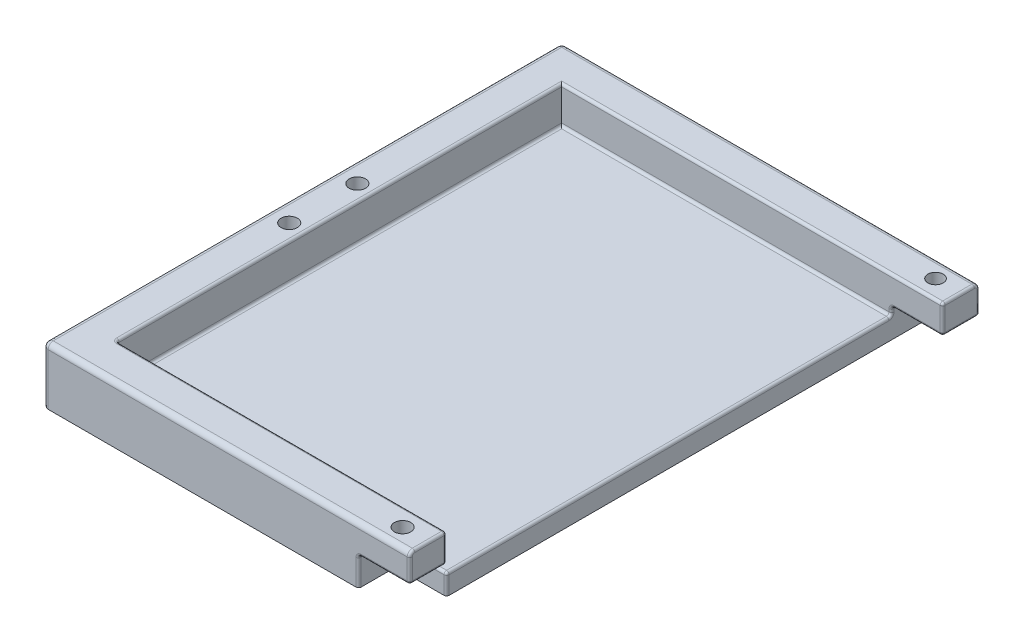
SolidWorks part; units mm, degrees
ref_plane "Front Plane" through (0, 0, 0) normal (0, 0, 1) x (1, 0, 0)
ref_plane "Top Plane" through (0, 0, 0) normal (0, 1, 0) x (1, 0, 0)
ref_plane "Right Plane" through (0, 0, 0) normal (1, 0, 0) x (0, 0, -1)
sketch "Sketch1" plane through (0, 0, 0) normal (0, 1, 0) x (1, 0, 0)
  line L1 (-35.85, 50.7) -> (35.85, 50.7)
  line L2 (-35.85, 50.7) -> (-35.85, -50.7)
  line L3 (-35.85, -50.7) -> (35.85, -50.7)
  line L4 (35.85, 50.7) -> (35.85, -50.7)
  line L5 (-35.85, 50.7) -> (35.85, -50.7) construction
  line L6 (-35.85, -50.7) -> (35.85, 50.7) construction
  point P0 (0, 0)
  dimension "D1" = 71.7
  dimension "D2" = 101.4
extrude "Boss-Extrude1" add sketch "Sketch1" along normal blind 11.1 contours L1 L4 L3 L2
sketch "Sketch5" plane through (35.85, 0, 0) normal (1, 0, 0) x (0, 0, -1)
  line L2 (-43.5, 18.4616) -> (-43.5, 4)
  line L3 (-43.5, 4) -> (43.5, 4)
  line L4 (0, 0) -> (0, 18.4616) construction
  line L5 (50.7, 0) -> (-50.7, 0) construction
  line L7 (-43.5, 18.4616) -> (43.5, 18.4616)
  line L8 (43.5, 18.4616) -> (43.5, 4)
  point P9 (0, 4)
  dimension "D1" = 87
  dimension "D3" = 4
extrude "Cut-Extrude1" cut sketch "Sketch5" against normal blind 64.5
fillet "Fillet2" radius 1 4 edges at (-35.85, 5.55, -50.7) (-35.85, 5.55, 50.7) (-35.85, 11.1, 0) (-35.85, 0, 0)
sketch "Sketch7" plane through (0, 11.1, 0) normal (0, 1, 0) x (1, 0, 0)
  line L0 (-35.85, 0) -> (0, 0) construction
  line L1 (-35.85, 50.7) -> (-35.85, -50.7) construction
  line L2 (-34.85, -6.6579) -> (-28.65, -6.6579) construction
  line L3 (-34.85, 50.7) -> (-34.85, -50.7) construction
  circle A0 centre (-31.75, -6.6579) radius 1.6
  circle A1 centre (-31.75, 6.6579) radius 1.6
  dimension "D1" = 3.2
  dimension "D2" = 6.6579
  dimension "D3" = 6.2
extrude "Cut-Extrude3" cut sketch "Sketch7" against normal blind 4
sketch "Sketch10" plane through (35.85, 0, 0) normal (1, 0, 0) x (0, 0, -1)
  line L0 (-43.5, 0) -> (-50.7, 0)
  line L1 (50.7, 0) -> (-50.7, 0) construction
  line L2 (-50.7, 11.1) -> (-50.7, 0) construction
  line L3 (-50.7, 5.55) -> (-50.7, 0)
  line L4 (-43.5, 5.55) -> (-43.5, 0)
  line L7 (-43.5, 11.1) -> (-43.5, 0) construction
  line L8 (-43.5, 11.1) -> (-43.5, 4) construction
  line L9 (-43.5, 5.55) -> (-43.5, 11.1)
  line L12 (-50.7, 5.55) -> (-43.5, 5.55)
  line M10 (-43.5, 4) -> (-43.5, 11.1)
  line M13 (-50.7, 11.1) -> (-50.7, 0)
  line M14 (-50.7, 0) -> (50.7, 0)
sketch "Sketch11" plane through (35.85, 0, 0) normal (1, 0, 0) x (0, 0, -1)
  line L0 (43.5, 11.1) -> (43.5, 0) construction
  line L1 (50.7, 0) -> (-50.7, 0) construction
  line L2 (50.7, 5.55) -> (50.7, 11.1)
  line L3 (50.7, 11.1) -> (43.5, 11.1) construction
  line L4 (43.5, 5.55) -> (50.7, 5.55)
  line L5 (50.7, 11.1) -> (50.7, 0) construction
  line L6 (50.7, 11.1) -> (43.5, 11.1)
  line L7 (43.5, 11.1) -> (50.7, 11.1)
  line L8 (43.5, 11.1) -> (43.5, 5.55)
  line M1 (50.7, 0) -> (50.7, 11.1)
  line M3 (50.7, 11.1) -> (43.5, 11.1)
  line M4 (43.5, 11.1) -> (43.5, 4)
extrude "Boss-Extrude2" add sketch "Sketch11" along normal blind 10 contours L4 M4 M1 M3 region at (35.85, 8.325, -47.1)
extrude "Cut-Extrude4" cut sketch "Sketch10" against normal blind 10 contours L12 L4 M13 M14 M10 region at (35.85, 2.775, 47.1)
fillet "Fillet4" radius 0.5 2 edges at (25.85, 5.55, 47.1)
fillet "Fillet7" radius 0.5 1 edges at (25.85, 2, 43.5)
fillet "Fillet8" radius 0.5 1 edges at (-1.4, 4, 43.5)
fillet "Fillet9" radius 0.5 4 edges at (-28.65, 7.8, 43.5) (-28.65, 4.1464, 43.3536) (-28.65, 4, -0.25) (3.6, 4, -43.5)
fillet "Fillet10" radius 0.5 2 edges at (45.85, 5.55, -47.1) (35.85, 5.55, 47.1)
sketch "Sketch12" plane through (0, 5.55, 0) normal (0, -1, 0) x (-1, 0, 0)
  line L0 (-35.35, -47.1) -> (-26.35, -47.1) construction
  line L3 (-26.35, -50.7) -> (-26.35, -43.5) construction
  line L4 (-35.35, -43.5) -> (-35.35, -50.7) construction
  circle A0 centre (-30.85, -47.1) radius 1.6
  dimension "D1" = 3.2
extrude "Cut-Extrude5" cut sketch "Sketch12" against normal blind 10
sketch "Sketch13" plane through (0, 5.55, 0) normal (0, -1, 0) x (1, 0, 0)
  line L0 (36.35, -47.1) -> (45.35, -47.1) construction
  line L1 (36.35, -43.5) -> (36.35, -50.7) construction
  line L3 (45.35, -50.7) -> (45.35, -43.5) construction
  circle A0 centre (40.85, -47.1) radius 1.5
  dimension "D1" = 3
extrude "Cut-Extrude6" cut sketch "Sketch13" against normal blind 10
fillet "Fillet11" radius 1 4 edges at (-35.5571, 10.8071, -50.4071) (-35.5571, 10.8071, 50.4071) (5.5, 11.1, -50.7) (0.5, 11.1, 50.7)
fillet "Fillet17" radius 0.5 2 edges at (25.9964, 4, 43.6464) (31.1, 4, 43.5)
fillet "Fillet19" radius 0.5 9 edges at (45.85, 8.575, -43.5) (45.7036, 5.6964, -43.5) (35.9964, 5.4036, -43.5) (35.85, 4.1464, -43.3536) (35.85, 4, 0) (35.85, 3.8536, 43.3536) (35.85, 1.75, 43.5)
fillet "Fillet20" radius 0.5 8 edges at (45.7036, 11.1, -43.6464) (45.85, 11.1, -46.85) (45.85, 10.8071, -50.4071) (45.85, 8.075, -50.7) (45.7036, 5.6964, -50.7) (35.9964, 5.4036, -50.7)
fillet "Fillet21" radius 0.5 16 edges at (-28.65, 11.1, -0.5) (-28.5036, 11.1, 43.3536) (3.85, 11.1, 43.5) (25.85, 4.1464, 43.3536) (25.85, 4.775, 43.5) (25.9964, 5.4036, 43.5) (30.85, 5.55, 43.5) (35.7036, 5.6964, 43.5) (35.85, 8.575, 43.5) (35.85, 11.1, 46.6) (35.85, 10.8071, 50.4071) (25.85, 2.525, 50.7) (25.9964, 5.4036, 50.7) (30.85, 5.55, 50.7) (35.7036, 5.6964, 50.7) (35.85, 8.075, 50.7)
